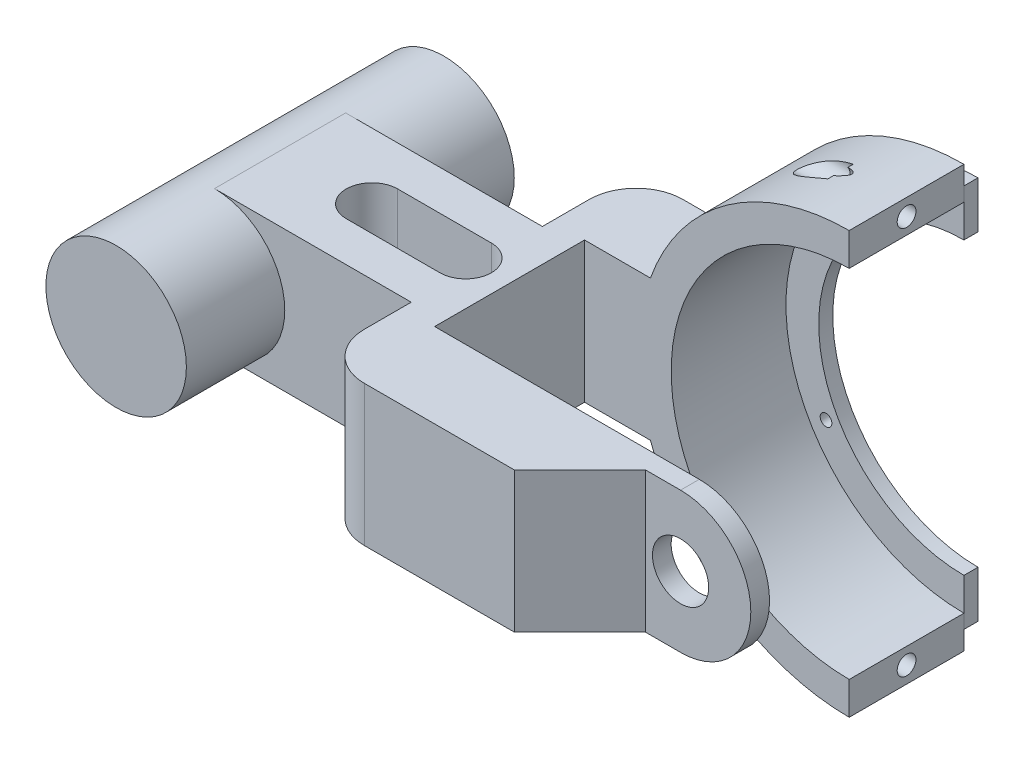
SolidWorks part; units mm, degrees
ref_plane "前视基准面" through (0, 0, 0) normal (0, 0, 1) x (1, 0, 0)
ref_plane "上视基准面" through (0, 0, 0) normal (0, 1, 0) x (1, 0, 0)
ref_plane "右视基准面" through (0, 0, 0) normal (1, 0, 0) x (0, 0, -1)
sketch "Sketch1" plane through (0, 0, 0) normal (0, 1, 0) x (1, 0, 0)
  line L0 (-29.4038, 20.0496) -> (-29.4038, -7.9504)
  line L1 (-29.4038, -7.9504) -> (12.5962, -7.9504)
  line L2 (12.5962, -7.9504) -> (12.5962, -27.9504)
  line L3 (12.5962, -27.9504) -> (83.5962, -27.9504)
  line L4 (83.5962, -27.9504) -> (83.5962, -9.9504)
  line L5 (83.5962, -9.9504) -> (19.5962, -9.9504)
  line L6 (19.5962, -9.9504) -> (19.5962, 22.0496)
  line L7 (19.5962, 22.0496) -> (83.5962, 22.0496)
  line L8 (83.5962, 22.0496) -> (83.5962, 40.0496)
  line L9 (83.5962, 40.0496) -> (12.5962, 40.0496)
  line L10 (12.5962, 40.0496) -> (12.5962, 20.0496)
  line L11 (12.5962, 20.0496) -> (-29.4038, 20.0496)
  point P13 (19.5962, 6.0496)
  point P14 (-29.4038, 6.0496)
  dimension "D1" = 32
  dimension "D2" = 28
  dimension "D3" = 71
  dimension "D4" = 42
  dimension "D5" = 20
  dimension "D6" = 71
extrude "Boss-Extrude1" add sketch "Sketch1" along normal blind 30
fillet "Fillet1" radius 10 2 edges at (12.5962, 15, -40.0496) (12.5962, 15, 27.9504)
sketch "Sketch3" plane through (0, 30, 0) normal (0, 1, 0) x (1, 0, 0)
  line L0 (-29.4038, 6.0496) -> (47.8406, 6.0496) construction
  line L1 (-29.4038, 20.0496) -> (-29.4038, -7.9504) construction
ref_plane "Plane1" through (0, 0, -6.0496) normal (0, 0, 1) x (1, 0, 0)
sketch "Sketch4" plane through (0, 0, -6.0496) normal (0, 0, 1) x (1, 0, 0)
  line L0 (-29.4038, 30) -> (-29.4038, 0) construction
  circle A1 centre (-29.4038, 15) radius 15
extrude "Boss-Extrude2" add sketch "Sketch4" along normal mid plane 70
sketch "Sketch5" plane through (0, 30, 0) normal (0, 1, 0) x (1, 0, 0)
  line L0 (54.5962, -27.9504) -> (68.5962, -13.9504)
  line L1 (22.5962, -27.9504) -> (83.5962, -27.9504) construction
  line L2 (68.5962, -13.9504) -> (83.5962, -13.9504)
  line L3 (83.5962, -27.9504) -> (83.5962, -9.9504) construction
  line L4 (54.5962, -27.9504) -> (83.5962, -27.9504)
  line L5 (83.5962, -27.9504) -> (83.5962, -13.9504)
  dimension "D1" = 4
  dimension "D2" = 45
  dimension "D3" = 15
extrude "Cut-Extrude1" cut sketch "Sketch5" against normal blind 70
sketch "Sketch6" plane through (0, 30, 0) normal (0, 1, 0) x (1, 0, 0)
  line L0 (-29.4038, 6.0496) -> (19.5962, 6.0496) construction
  line L1 (-29.4038, 20.0496) -> (-29.4038, -7.9504) construction
  line L2 (19.5962, -9.9504) -> (19.5962, 22.0496) construction
sketch "Sketch8" plane through (0, 0, 13.9504) normal (0, 0, 1) x (1, 0, 0)
  line L0 (68.5962, 30) -> (83.5962, 0) construction
  line L1 (83.5962, 0) -> (83.5962, 30) construction
  line L2 (83.5962, 30) -> (68.5962, 0) construction
  circle A0 centre (76.0962, 15) radius 6
extrude "Cut-Extrude2" cut sketch "Sketch8" against normal blind 100
sketch "Sketch9" plane through (83.5962, 0, 0) normal (1, 0, 0) x (0, 0, -1)
  line L1 (-13.9504, 30) -> (-9.9504, 30)
  line L2 (-13.9504, 30) -> (-13.9504, 0)
  line L3 (-13.9504, 0) -> (-9.9504, 0)
  line L4 (-9.9504, 30) -> (-9.9504, 0)
extrude "Boss-Extrude3" add sketch "Sketch9" along normal blind 10
sketch "Sketch13" plane through (0, 0, -40.0496) normal (0, 0, -1) x (-1, 0, 0)
  line L1 (-76.0962, -30) -> (-76.0962, 60)
  arc A0 (-66.6618, -23) -> (-69.4608, 53.5873) centre (-76.0962, 15) ccw construction
  arc A1 (-76.0962, -30) -> (-76.0962, 60) centre (-76.0962, 15) ccw
sketch "Sketch14" plane through (0, 0, 13.9504) normal (0, 0, 1) x (1, 0, 0)
  line L0 (93.5962, 30) -> (68.5962, 30) construction
  line L1 (93.5962, 0) -> (68.5962, 0) construction
  line L2 (76.0962, 30) -> (93.5962, 30)
  line L3 (93.5962, 30) -> (93.5962, 0)
  line L4 (93.5962, 0) -> (76.0962, 0)
  arc A0 (76.0962, 30) -> (76.0962, 0) centre (76.0962, 15) cw
extrude "Cut-Extrude4" cut sketch "Sketch14" against normal blind 15
extrude "Boss-Extrude4" add sketch "Sketch13" against normal up to surface (18 mm away) up to face at (70.0962, 15, -22.0496)
sketch "Sketch16" plane through (0, 0, -40.0496) normal (0, 0, -1) x (-1, 0, 0)
  line L0 (-76.0962, 21) -> (-76.0962, 9) construction
  line L1 (-76.0962, 0) -> (-76.0962, -30) construction
  line L2 (-76.0962, 60) -> (-76.0962, 30) construction
  line L3 (-76.0962, 53) -> (-76.0962, -23)
  line L4 (-83.5962, 0) -> (-76.0962, 0) construction
  arc A0 (-76.0962, -23) -> (-76.0962, 53) centre (-76.0962, 15) ccw
  arc A1 (-76.0962, 30) -> (-76.0962, 0) centre (-76.0962, 15) cw
  line M3 (-76.0962, 21) -> (-76.0962, 9)
  arc M4 (-76.0962, 9) -> (-76.0962, 21) centre (-76.0962, 15) cw
  line M5 (-83.5962, 0) -> (-76.0962, 0)
  line M6 (-76.0962, 0) -> (-76.0962, -30)
  line M12 (-76.0962, 60) -> (-76.0962, 30)
  line M13 (-76.0962, 30) -> (-83.5962, 30)
  line M14 (-83.5962, 30) -> (-83.5962, 0)
extrude "Cut-Extrude8" cut sketch "Sketch16" against normal up to surface (18 mm away) contours A1 A0 M12 M6 | L3 M13 M14 M5 M4 | A1 L3 M3 region at (58.1667, 15, -40.0496) region at (69.73, 15, -40.0496) region at (76.4054, 25.5, -40.0496) up to face at (79.0962, 15, -22.0496)
sketch "Sketch17" plane through (0, 0, -40.0496) normal (0, 0, -1) x (-1, 0, 0)
  line L0 (-76.0962, 60) -> (-76.0962, 53) construction
  line L1 (-76.0962, 60) -> (-76.0962, 53)
  line L2 (-68.2046, -22.1715) -> (-68.2046, -29.3026)
  arc A0 (-76.0962, 60) -> (-68.2046, -29.3026) centre (-76.0962, 15) ccw
  arc A1 (-76.0962, -30) -> (-33.6698, 0) centre (-76.0962, 15) ccw construction
  arc A2 (-76.0962, 53) -> (-68.2046, -22.1715) centre (-76.0962, 15) ccw
  arc A3 (-76.0962, -23) -> (-76.0962, 53) centre (-76.0962, 15) ccw construction
extrude "Boss-Extrude5" add sketch "Sketch17" against normal up to surface (18 mm away) up to face at (45.4227, 15, -22.0496)
sketch "Sketch18" plane through (0, 0, -40.0496) normal (0, 0, -1) x (-1, 0, 0)
  circle A0 centre (-76.0962, 15) radius 38
  circle A2 centre (-76.0962, 15) radius 45
extrude "Boss-Extrude6" add sketch "Sketch18" along normal blind 6.5
sketch "Sketch20" plane through (0, 0, -46.5496) normal (0, 0, -1) x (-1, 0, 0)
  circle A0 centre (-76.0962, 15) radius 34 construction
  circle A2 centre (-76.0962, 15) radius 31
  circle A3 centre (-76.0962, 15) radius 41
extrude "Boss-Extrude7" add sketch "Sketch20" along normal blind 3 separate body
sketch "Sketch24" plane through (0, 0, -49.5496) normal (0, 0, -1) x (-1, 0, 0)
  circle A0 centre (-76.0962, 15) radius 34 construction
  circle A14 centre (-46.6513, 32) radius 1.5
  circle A15 centre (-46.6513, -2) radius 1.5
  circle A17 centre (-105.541, -2) radius 1.5
  circle A18 centre (-105.541, 32) radius 1.5
  point P17 (-76.0962, 15)
  point P18 (-68.0962, 15)
  point P19 (-72.0962, 15)
sketch "Sketch25" plane through (0, 0, -49.5496) normal (0, 0, -1) x (-1, 0, 0)
  line L1 (-142.1505, 71.9535) -> (-76.0962, 71.9535)
  line L2 (-142.1505, 71.9535) -> (-142.1505, -36.0053)
  line L3 (-142.1505, -36.0053) -> (-76.0962, -36.0053)
  line L4 (-76.0962, 71.9535) -> (-76.0962, -36.0053)
extrude "Cut-Extrude15" cut sketch "Sketch25" against normal up to surface (27.5 mm away) up to face at (38.0962, 15, -22.0496)
sketch "Sketch27" plane through (0, 0, 0) normal (1, 0, 0) x (0, 0, -1)
  line L0 (34.2996, 60) -> (34.2996, -30) construction
  line L1 (22.0496, 60) -> (46.5496, 60) construction
  line L2 (22.0496, 60) -> (22.0496, -30) construction
  line L3 (22.0496, -30) -> (46.5496, -30) construction
  line L4 (46.5496, 60) -> (46.5496, -30) construction
  line L5 (22.0496, 15) -> (4.8013, 15) construction
  circle A0 centre (34.2996, 56.457) radius 2
  circle A1 centre (34.2996, -26.457) radius 2
extrude "Cut-Extrude18" cut sketch "Sketch27" along normal blind 1000
sketch "Sketch28" plane through (0, 30, 0) normal (0, 1, 0) x (1, 0, 0)
  line L0 (-29.4038, 20.0496) -> (-29.4038, -7.9504) construction
  line L1 (-29.4038, 6.0496) -> (19.5962, 6.0496) construction
  line L4 (19.5962, -9.9504) -> (19.5962, 22.0496) construction
  line L5 (-9.7831, 6.0496) -> (10.2169, 6.0496) construction
  line L6 (-9.7831, 11.5496) -> (10.2169, 11.5496)
  line L7 (-9.7831, 0.5496) -> (10.2169, 0.5496)
  arc A2 (-9.7831, 11.5496) -> (-9.7831, 0.5496) centre (-9.7831, 6.0496) ccw
  arc A3 (10.2169, 0.5496) -> (10.2169, 11.5496) centre (10.2169, 6.0496) ccw
  point P10 (0.2169, 6.0496)
  dimension "D1" = 5.5
  dimension "D2" = 20
extrude "Cut-Extrude19" cut sketch "Sketch28" against normal through all
sketch "Sketch29" plane through (0, 0, 0) normal (1, 0, 0) x (0, 0, -1)
  circle A0 centre (34.2996, 56.457) radius 3
  circle A1 centre (34.2996, -26.457) radius 3
extrude "Cut-Extrude20" cut sketch "Sketch29" along normal blind 62
hole_wizard "M3 Tapped Hole1" positions "3DSketch1" profile "Sketch31" tap size "M3" standard "GB" end condition through all
sketch3d "3DSketch1"
  point P0 (46.6513, 32, -49.5496)
  point P3 (46.6513, -2, -49.5496)
sketch "Sketch31" plane through (46.6513, 32, -49.5496) normal (1, 0, 0) x (0, 1, 0)
  line L0 (0, 0) -> (0, 78.5)
  line L1 (0, 78.5) -> (1.25, 78.5)
  line L2 (1.25, 78.5) -> (1.25, 0)
  line L5 (1.25, 0) -> (0, 0)
  line L11 (0, -6.35) -> (0, 107.95) construction
  dimension "Thru Tap Drill Dia." = 2.5
  dimension "Thru Tap Drill Depth" = 78.5
cosmetic thread "Hole Thread1" parameters "D2"=3
cosmetic thread "Hole Thread2" parameters "D2"=3
